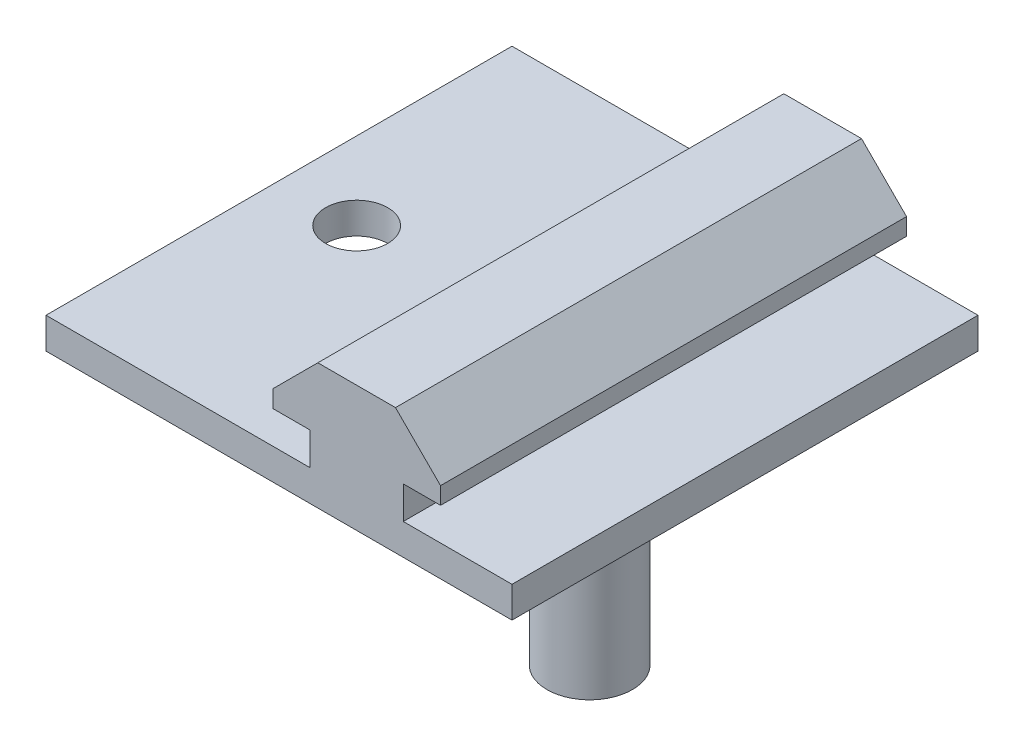
SolidWorks part; units mm, degrees
ref_plane "Front Plane" through (0, 0, 0) normal (0, 0, 1) x (1, 0, 0)
ref_plane "Top Plane" through (0, 0, 0) normal (0, 1, 0) x (1, 0, 0)
ref_plane "Right Plane" through (0, 0, 0) normal (1, 0, 0) x (0, 0, -1)
sketch "Sketch2" plane through (0, 0, 0) normal (0, 0, 1) x (1, 0, 0)
  line L0 (5.4, 3.2) -> (2.5, 6.1)
  line L1 (5.4, 2.1) -> (5.4, 3.2)
  line L2 (-3, 2.1) -> (-3, 0)
  line L3 (3, 2.1) -> (5.4, 2.1)
  line L5 (-3, 2.1) -> (-5.4, 2.1)
  line L6 (-5.4, 2.1) -> (-5.4, 3.2)
  line L7 (-5.4, 3.2) -> (-2.5, 6.1)
  line L8 (-2.5, 6.1) -> (2.5, 6.1)
  line L9 (0, -55) -> (0, 55) construction
  line L18 (-3, 0) -> (-20, 0)
  line L27 (55, 0) -> (-55, 0) construction
  line L29 (3, 2.1) -> (3, 0)
  line L30 (-20, 0) -> (-20, -2)
  line L34 (0, 12.2875) -> (0, -5.4011) construction
  line L38 (-20, -2) -> (10, -2)
  line L40 (3, 0) -> (10, 0)
  line L42 (10, -2) -> (10, 0)
  point P2 (0, 6.1)
  dimension "D1" = 270
  dimension "D2" = 1.1
  dimension "D3" = 10
  dimension "D4" = 20
  dimension "5.4" = 5.4
  dimension "D6" = 4
  dimension "D7" = 2.1
  dimension "D8" = 2
extrude "Boss-Extrude2" add sketch "Sketch2" along normal mid plane 30
sketch "Sketch4" plane through (7, 0, 0) normal (0, -1, 0) x (0, 0, 1)
  line L0 (0, 2.545) -> (0, 11.455) construction
  line L2 (15, 27) -> (-15, 27) construction
  circle A0 centre (0, 22) radius 2
  dimension "D1" = 4
  dimension "D2" = 5
extrude "Cut-Extrude1" cut sketch "Sketch4" along normal through all
sketch "Sketch5" plane through (0, -2, 0) normal (0, -1, 0) x (1, 0, 0)
  circle A0 centre (0, 0) radius 2.75
  dimension "D1" = 5.5
extrude "Boss-Extrude3" add sketch "Sketch5" along normal blind 15
